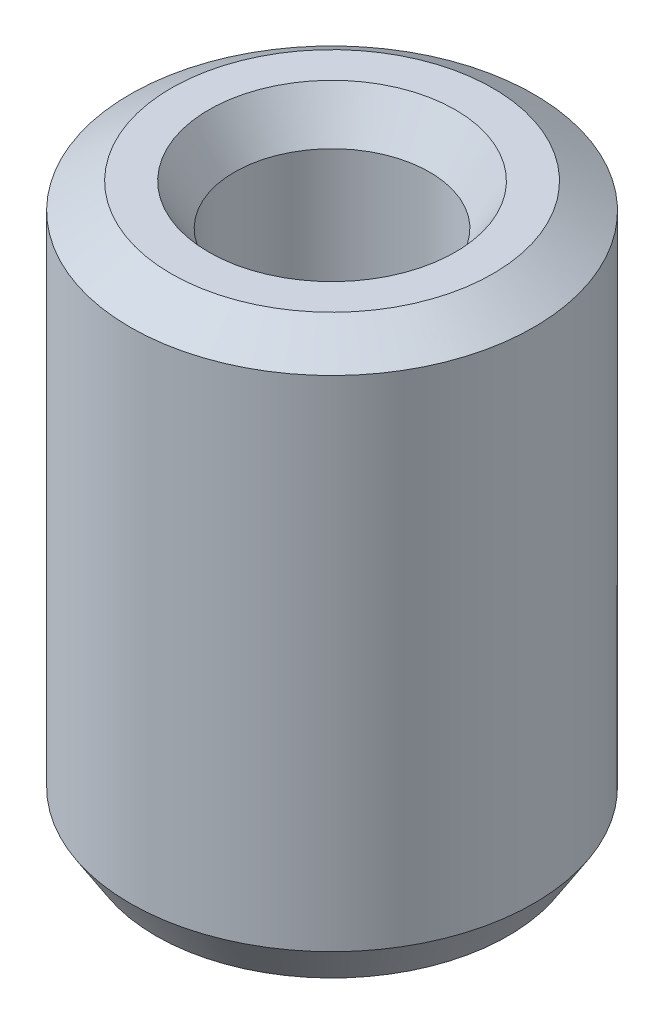
SolidWorks part; units mm, degrees
ref_plane "Front Plane" through (0, 0, 0) normal (0, 0, 1) x (1, 0, 0)
ref_plane "Top Plane" through (0, 0, 0) normal (0, 1, 0) x (1, 0, 0)
ref_plane "Right Plane" through (0, 0, 0) normal (1, 0, 0) x (0, 0, -1)
sketch "Sketch1" plane through (0, 0, 0) normal (0, 1, 0) x (1, 0, 0)
  circle A0 centre (0, 0) radius 5
  dimension "SLEEVE_OD" = 10
extrude "Boss-Extrude1" add sketch "Sketch1" along normal blind 14.0149
sketch "Sketch2" plane through (0, 0, 0) normal (0, 1, 0) x (1, 0, 0)
  circle A0 centre (0, 0) radius 2.4158
  dimension "BORE_D" = 4.8315
extrude "Cut-Extrude1" cut sketch "Sketch2" along normal through all
chamfer "Chamfer1" distance 0.6389 angle 57.837 4 edges at (0, 14.0149, 2.4158) (0, 0, 2.4158) (0, 0, 5) (0, 14.0149, 5) first distance on face at (0, 14.0149, 2.4158) first distance on face at (0, 0, 2.4158) first distance on face at (0, 14.0149, 5)
